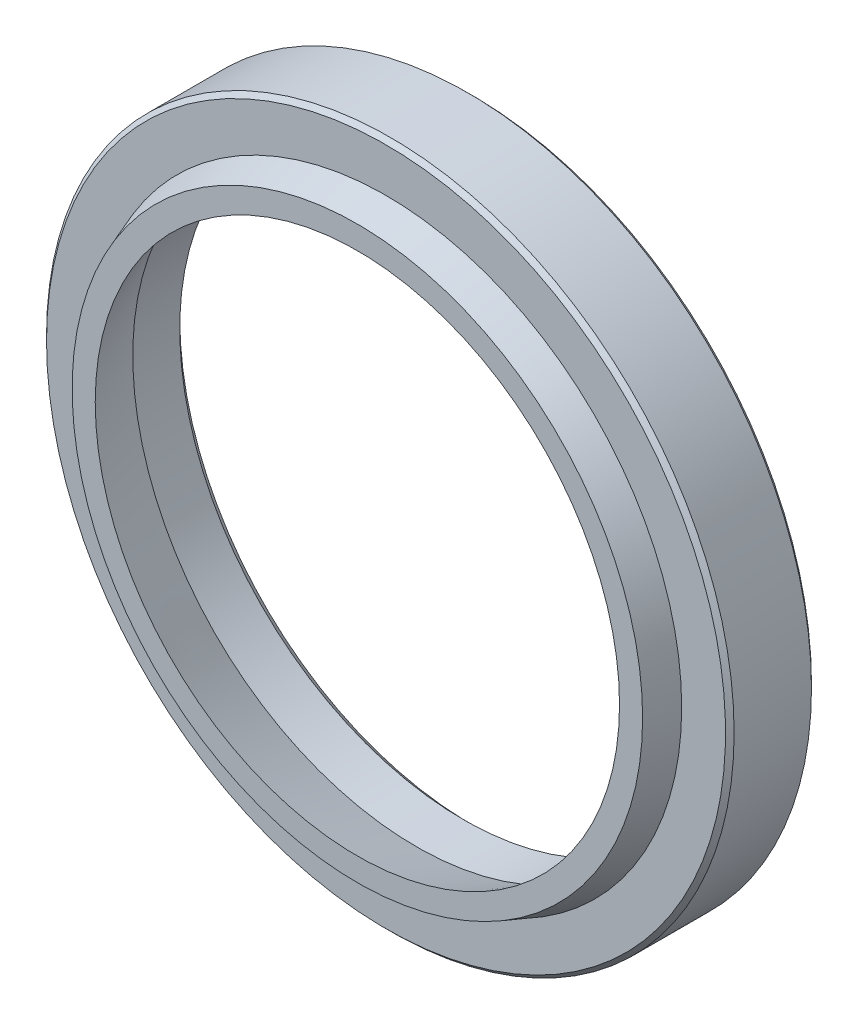
SolidWorks part; units mm, degrees
ref_plane "Front" through (0, 0, 0) normal (0, 0, 1) x (1, 0, 0)
ref_plane "Top" through (0, 0, 0) normal (0, 1, 0) x (1, 0, 0)
ref_plane "Right" through (0, 0, 0) normal (1, 0, 0) x (0, 0, -1)
sketch "Sketch1" plane through (0, 0, 0) normal (0, 1, 0) x (-1, 0, 0)
  line L0 (0, 9.1959) -> (0, -4.6797) construction
  line L1 (16.5, -6.6667) -> (16.5, -3.4343)
  line L2 (16.5, -6.6667) -> (20, -6.6667)
  line L3 (16.5, -3.4343) -> (15.25, 0)
  line L4 (17.2, -1.6667) -> (20, -1.6667)
  line L5 (20, -6.6667) -> (20, -1.6667)
  line L6 (15.25, 0) -> (16.5934, 0)
  line L7 (16.5934, 0) -> (17.2, -1.6667)
  dimension "D1" = 30.5
  dimension "D5" = 160
  dimension "D6" = 0.7
  dimension "D7" = 1.6667
revolve "Body" add sketch "Sketch1" angle 360 about L0
chamfer "EndChamfer" distance 0.5 angle 45 1 edges at (16.5, 0, -6.6667)
chamfer "BodyChamfer" distance 0.25 angle 45 2 edges at (20, 0, -1.6667) (20, 0, -6.6667)
equation "\"D7@Sketch1\" = \"h@Sketch1\" / 3"
equation "\"D6@Sketch1\" = \"S@Sketch1\" / 5"
equation "\"D1@EndChamfer\" = \"S@Sketch1\" / 7"
equation "\"D1@BodyChamfer\" = \"S@Sketch1\" / 14"
